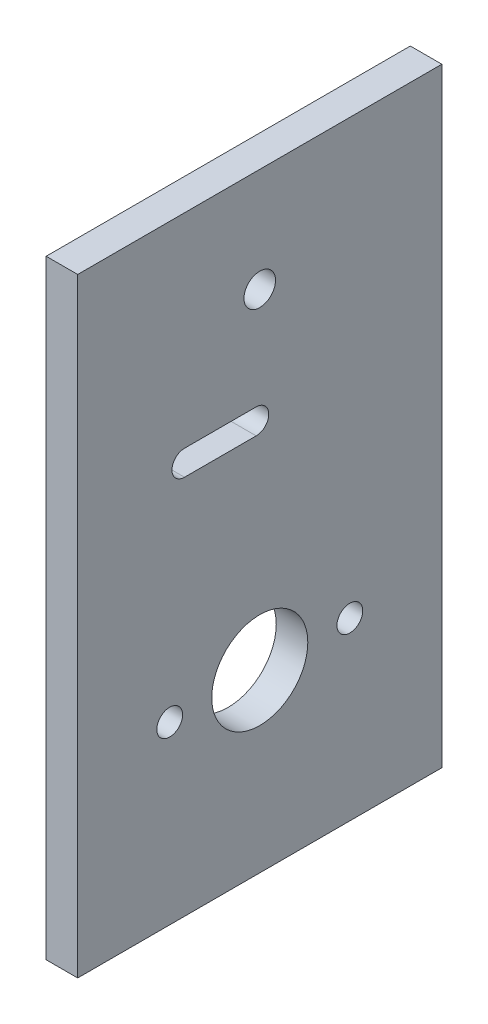
SolidWorks part; units mm, degrees
ref_plane "Front Plane" through (0, 0, 0) normal (0, 0, 1) x (1, 0, 0)
ref_plane "Top Plane" through (0, 0, 0) normal (0, 1, 0) x (1, 0, 0)
ref_plane "Right Plane" through (0, 0, 0) normal (1, 0, 0) x (0, 0, -1)
sketch "Sketch1" plane through (0, 0, 0) normal (1, 0, 0) x (0, 0, -1)
  line L1 (-25.4, -42.5) -> (25.4, -42.5)
  line L2 (-25.4, -42.5) -> (-25.4, 42.5)
  line L3 (-25.4, 42.5) -> (25.4, 42.5)
  line L4 (25.4, -42.5) -> (25.4, 42.5)
  line L5 (-25.4, -42.5) -> (25.4, 42.5) construction
  line L6 (-25.4, 42.5) -> (25.4, -42.5) construction
  point P0 (0, 0)
  dimension "D1" = 85
  dimension "D2" = 50.8
extrude "Boss-Extrude1" add sketch "Sketch1" along normal blind 4.4
sketch "Sketch2" plane through (4.4, 0, 0) normal (1, 0, 0) x (0, 0, -1)
  line L0 (0, 27.9995) -> (0, -18.0005) construction
  line L1 (-12.565, -18.0005) -> (12.565, -18.0005) construction
  circle A0 centre (0, 27.9995) radius 2.2
  circle A1 centre (0, -18.0005) radius 6.7
  circle A2 centre (-12.565, -18.0005) radius 1.8
  circle A3 centre (12.565, -18.0005) radius 1.8
  point P3 (0, -19.5415)
  point P4 (0, 4.9995)
  point P9 (0, 31.9995)
  point P12 (0, -18.0005)
  dimension "D2" = 4.4
  dimension "D3" = 13.4
  dimension "D4" = 3.6
  dimension "D1" = 46
  dimension "D5" = 25.13
extrude "Cut-Extrude1" cut sketch "Sketch2" against normal through all
sketch "Sketch3" plane through (4.4, 0, 0) normal (1, 0, 0) x (0, 0, -1)
  line L0 (-6.1688, 25.2593) -> (-1.2504, 14.1873)
  line L1 (0, -18.0005) -> (0, 27.9995) construction
  line L2 (-2.8255, 8.4956) -> (-13.4013, 1.0599)
  line L3 (0, 12.2995) -> (-5.5, 12.2995) construction
  line L5 (0, 12.2995) -> (0, 5.2995) construction
  line L7 (21.7397, -9.6175) -> (6.298, 30.4281)
  circle A0 centre (0, 27.9995) radius 6.75 construction
  circle A1 centre (0, -18.0005) radius 23.3 construction
  circle A2 centre (-5.5, 12.2995) radius 4.65 construction
  arc A3 (-6.1688, 25.2593) -> (6.298, 30.4281) centre (0, 27.9995) cw
  arc A4 (-2.8255, 8.4956) -> (-1.2504, 14.1873) centre (-5.5, 12.2995) ccw
  arc A5 (-13.4013, 1.0599) -> (21.7397, -9.6175) centre (0, -18.0005) ccw
  point P5 (0.652, 12.2995)
  point P13 (0, 12.2995)
  point P14 (-5.4486, 12.2995)
  dimension "D1" = 46.6
  dimension "D2" = 13.5
  dimension "D4" = 46
  dimension "D5" = 7
  dimension "D3" = 9.3
  dimension "D6" = 5.5
sketch "Sketch4" plane through (4.4, 0, 0) normal (1, 0, 0) x (0, 0, -1)
  line L0 (-10.5, 12.2995) -> (-0.5, 12.2995) construction
  line L1 (-10.5, 14.0495) -> (-0.5, 14.0495)
  line L2 (-10.5, 10.5495) -> (-0.5, 10.5495)
  arc A0 (-10.5, 14.0495) -> (-10.5, 10.5495) centre (-10.5, 12.2995) ccw
  arc A2 (-0.5, 10.5495) -> (-0.5, 14.0495) centre (-0.5, 12.2995) ccw
  point P5 (-5.5, 12.2995)
  dimension "D2" = 3.5
  dimension "D3" = 10
extrude "Cut-Extrude2" cut sketch "Sketch4" against normal through all
sketch "Sketch5" plane through (0, 0, 0) normal (-1, 0, 0) x (0, 0, 1)
  circle A0 centre (0, 27.9995) radius 4.25
  circle A1 centre (0, 27.9995) radius 8
  dimension "D1" = 8.5
  dimension "D2" = 16
extrude "Boss-Extrude2" add sketch "Sketch5" along normal blind 4.3
chamfer "Chamfer1" distance 1 angle 45 1 edges at (0, 27.9995, 8)
equation "\"motor_pulley\"=50"
